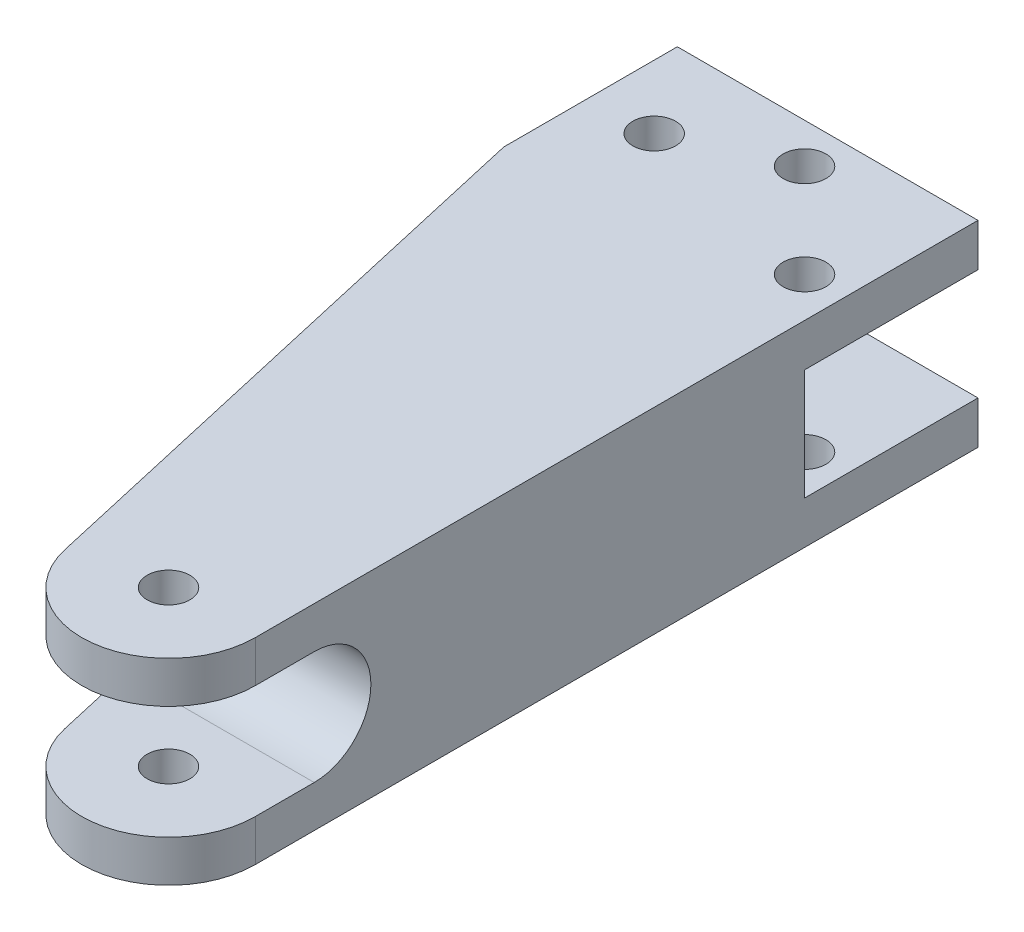
SolidWorks part; units mm, degrees
material "Cast Alloy Steel"
ref_plane "Front Plane" through (0, 0, 0) normal (0, 0, 1) x (1, 0, 0)
ref_plane "Top Plane" through (0, 0, 0) normal (0, 1, 0) x (1, 0, 0)
ref_plane "Right Plane" through (0, 0, 0) normal (1, 0, 0) x (0, 0, -1)
sketch "Sketch1" plane through (0, 0, 0) normal (0, 0, 1) x (1, 0, 0)
  line L0 (-9.525, -10.795) -> (9.525, -10.795)
  line L1 (-9.525, -10.795) -> (-9.525, 10.795)
  line L2 (9.525, -10.795) -> (9.525, 10.795)
  line L3 (-9.525, 10.795) -> (9.525, 10.795)
  line L4 (-9.525, -10.795) -> (9.525, 10.795) construction
  line L5 (9.525, -10.795) -> (-9.525, 10.795) construction
  point P1 (0, 0)
  dimension "D1" = 21.59
  dimension "D2" = 19.05
extrude "Boss-Extrude1" add sketch "Sketch1" along normal blind 88.9
sketch "Sketch3" plane through (0, 10.795, 0) normal (0, 1, 0) x (1, 0, 0)
  line L0 (-9.525, -88.9) -> (-9.525, 0) construction
  line L1 (9.525, -88.9) -> (9.525, 0) construction
  line L2 (9.525, -88.9) -> (-9.525, -88.9) construction
  arc A0 (-9.525, -79.375) -> (9.525, -79.375) centre (0, -79.375) ccw
  point P3 (-9.525, -74.1407)
  point P6 (9.525, -80.3913)
  point P11 (-9.525, -79.8332)
extrude "Cut-Extrude-Thin1" cut sketch "Sketch3" against normal blind 88.9 and the other way through all thin thin type one direction wall 25.4
sketch "Sketch4" plane through (0, 10.795, 0) normal (0, 1, 0) x (1, 0, 0)
  line L0 (5.1435, -14.6685) -> (9.525, -14.6685) construction
  line L1 (9.525, -79.375) -> (9.525, 0) construction
  line L2 (-9.525, 0) -> (9.525, -19.05) construction
  line L3 (-5.1435, -4.3815) -> (-5.1435, 0) construction
  line L4 (-9.525, 0) -> (9.525, 0) construction
  line L5 (-9.525, 0) -> (-9.525, -19.05) construction
  line L6 (-9.525, -19.05) -> (9.525, -19.05) construction
  line L7 (9.525, 0) -> (9.525, -19.05) construction
  circle A0 centre (0, -79.375) radius 2.3495
  circle A1 centre (5.1435, -14.6685) radius 2.3495
  circle A2 centre (-5.1435, -4.3815) radius 2.3495
  dimension "D1" = 4.699
  dimension "D2" = 4.3815
  dimension "D3" = 4.3815
extrude "Cut-Extrude1" cut sketch "Sketch4" against normal through all
sketch "Sketch5" plane through (0, 10.795, 0) normal (0, 1, 0) x (1, 0, 0)
  line L0 (-9.525, 0) -> (-23.495, 0)
  line L1 (-23.495, 0) -> (-23.495, -19.05)
  line L2 (-9.525, -79.375) -> (-9.525, 0) construction
  line L3 (-9.525, -79.375) -> (-9.525, 0)
  line L4 (-23.495, -19.05) -> (-9.2876, -81.4883)
  arc A0 (-9.525, -79.375) -> (9.525, -79.375) centre (0, -79.375) ccw construction
  arc A1 (-9.525, -79.375) -> (9.525, -79.375) centre (0, -79.375) ccw
  circle A2 centre (-16.51, -9.525) radius 2.3495
  circle A3 centre (-5.1435, -4.3815) radius 2.3495 construction
  point P2 (0, 0)
  point P13 (0, 0)
  point P14 (-16.51, 0)
  point P15 (0, 0)
  point P16 (0, 0)
  point P17 (-23.495, -9.525)
  line M9 (-9.525, 0) -> (-9.525, -79.375)
  arc M10 (-9.525, -79.375) -> (9.525, -79.375) centre (0, -79.375) ccw
  dimension "D1" = 13.97
  dimension "D2" = 19.05
  dimension "D3" = 12.819
extrude "Boss-Extrude2" add sketch "Sketch5" against normal up to surface (21.59 mm away) contours L1 L4 L0 A2 M10 M9 region at (-15.0361, 10.795, 28.5077) up to face at (0, -10.795, 81.7245)
sketch "Sketch6" plane through (9.525, 0, 0) normal (1, 0, 0) x (0, 0, -1)
  line L0 (19.05, -6.096) -> (19.05, 6.096)
  line L1 (19.05, -6.096) -> (-19.05, -6.096)
  line L2 (19.05, 6.096) -> (-19.05, 6.096)
  line L3 (-19.05, -6.096) -> (-19.05, 6.096)
  line L4 (19.05, -6.096) -> (-19.05, 6.096) construction
  line L5 (19.05, 6.096) -> (-19.05, -6.096) construction
  line L6 (-92.075, -6.223) -> (-72.898, -6.223)
  line L7 (-92.075, -6.223) -> (-92.075, 6.223)
  line L9 (-92.075, 6.223) -> (-72.898, 6.223)
  line L10 (-92.075, -6.223) -> (-69.1843, 4.9934) construction
  line L11 (-69.1843, -4.9934) -> (-92.075, 6.223) construction
  line L12 (-79.375, -10.795) -> (-79.375, 10.795) construction
  line L13 (-79.375, -10.795) -> (-79.375, 10.795) construction
  arc A0 (-72.898, 6.223) -> (-72.898, -6.223) centre (-72.898, 0) cw
  point P1 (0, 0)
  point P2 (-79.375, 0)
  point P14 (-79.375, 0)
  dimension "D1" = 12.192
  dimension "D2" = 19.05
extrude "Cut-Extrude2" cut sketch "Sketch6" against normal through all
